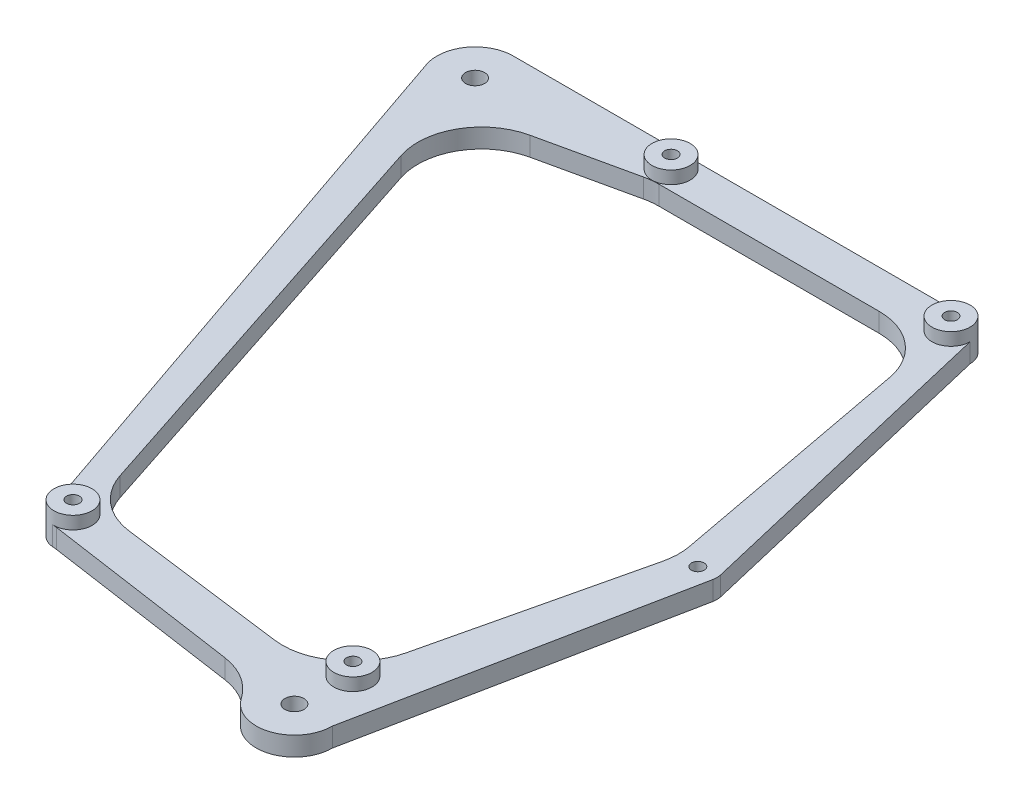
SolidWorks part; units mm, degrees
ref_plane "Front Plane" through (0, 0, 0) normal (0, 0, 1) x (1, 0, 0)
ref_plane "Top Plane" through (0, 0, 0) normal (0, 1, 0) x (1, 0, 0)
ref_plane "Right Plane" through (0, 0, 0) normal (1, 0, 0) x (0, 0, -1)
sketch "Sketch1" plane through (0, 53.5, 0) normal (0, 1, 0) x (1, 0, 0)
  circle A0 centre (-36, -88.75) radius 1.5 construction
  circle A1 centre (-36, -88.75) radius 6 construction
  circle A2 centre (35, 10.65) radius 1.5 construction
  circle A3 centre (35, 10.65) radius 6 construction
  circle A4 centre (106, -88.75) radius 1.5 construction
  circle A5 centre (106, -88.75) radius 6 construction
  circle A6 centre (-36, -88.75) radius 1.5
  circle A7 centre (-36, -88.75) radius 6
  circle A8 centre (35, 10.65) radius 1.5
  circle A9 centre (35, 10.65) radius 6
  circle A10 centre (106, -88.75) radius 1.5
  circle A11 centre (106, -88.75) radius 6
  circle A12 centre (119, -38.35) radius 1 construction
  circle A13 centre (-49, -38.35) radius 1 construction
  circle A14 centre (119, -38.35) radius 1
  circle A15 centre (-49, -38.35) radius 1
  circle A16 centre (119, -38.35) radius 3
  circle A17 centre (-49, -38.35) radius 3
  dimension "D1" = 2
  dimension "D2" = 2
extrude "AudioHolder links" add sketch "Sketch1" along normal blind 3
sketch "Limit profile" plane through (0, 53.5, 0) normal (0, -1, 0) x (1, 0, 0)
  line L4 (-47, -19.15) -> (117, -19.15)
  line L5 (117, -19.15) -> (117, 95.85)
  line L6 (117, 95.85) -> (-47, 95.85)
  line L7 (-47, 95.85) -> (-47, -19.15)
  line L8 (-47, -19.15) -> (117, -19.15)
  line L9 (117, -19.15) -> (117, 95.85)
  line L10 (117, 95.85) -> (-47, 95.85)
  line L11 (-47, 95.85) -> (-47, -19.15)
  dimension "D1" = 0
sketch "Sketch3" plane through (0, 56.5, 0) normal (0, 1, 0) x (1, 0, 0)
  line L0 (117, 19.15) -> (117, -95.85) construction
  line L1 (38.8, 17.05) -> (117, 17.05) construction
  line L2 (38.8, 17.05) -> (38.8, -83.75) construction
  line L3 (38.8, -83.75) -> (117, -83.75) construction
  line L4 (117, 17.05) -> (117, -83.75) construction
  line L5 (62.8, 13.65) -> (106.8, 13.65) construction
  line L6 (62.8, 13.65) -> (62.8, -80.35) construction
  line L7 (62.8, -80.35) -> (106.8, -80.35) construction
  line L8 (106.8, 13.65) -> (106.8, -80.35) construction
  line L10 (35, 16.65) -> (62.8, 16.65) construction
  circle A0 centre (106.8, 13.65) radius 1
  circle A1 centre (62.8, 13.65) radius 1
  circle A2 centre (62.8, -80.35) radius 1
  circle A3 centre (106.8, -80.35) radius 1
  circle A4 centre (106.8, 13.65) radius 3
  circle A5 centre (62.8, 13.65) radius 3
  circle A6 centre (62.8, -80.35) radius 3
  circle A7 centre (106.8, -80.35) radius 3
  circle A8 centre (35, 10.65) radius 6 construction
  circle A9 centre (35, 10.65) radius 6 construction
  point P4 (62.8, -33.35)
  point P9 (38.8, -33.35)
  dimension "D7" = 2
  dimension "D8" = 2
  dimension "D1" = 78.2
  dimension "D2" = 100.8
  dimension "D3" = 44
  dimension "D4" = 94
  dimension "D5" = 10.2
extrude "Modem standoffs" add sketch "Sketch3" along normal blind 2 and the other way up to surface (3 mm away) other way up to face at (106, 53.5, 94.75)
sketch "Sketch4" plane through (0, 53.5, 0) normal (0, -1, 0) x (1, 0, 0)
  line L0 (109.8, -13.65) -> (121.9197, 37.6604)
  line L1 (112, 88.75) -> (121.942, 38.9372)
  line L2 (106.8, 77.35) -> (116, 38.35)
  line L3 (116, 38.35) -> (106.8, -10.65)
  line L4 (106.8, -16.65) -> (62.8, -16.65)
  line L5 (62.8, -16.65) -> (35, -16.65)
  line L6 (100, 88.75) -> (62.8, 83.35)
  line L7 (63.1864, 77.375) -> (105.0953, 82.8186)
  line L8 (36.295, -4.7914) -> (62.8, -10.65)
  line L9 (62.8, -10.65) -> (106.8, -10.65)
  circle A0 centre (119, 38.35) radius 1 construction
  circle A1 centre (119, 38.35) radius 3 construction
  circle A2 centre (106.8, -13.65) radius 1 construction
  circle A3 centre (106.8, -13.65) radius 3 construction
  circle A4 centre (62.8, -13.65) radius 1 construction
  circle A5 centre (62.8, -13.65) radius 3 construction
  circle A6 centre (35, -10.65) radius 1.5 construction
  circle A7 centre (35, -10.65) radius 6 construction
  circle A8 centre (119, 38.35) radius 1
  arc A9 (121.9197, 37.6604) -> (121.942, 38.9372) centre (119, 38.35) ccw
  circle A10 centre (106.8, -13.65) radius 1
  arc A11 (106.8, -16.65) -> (109.8, -13.65) centre (106.8, -13.65) ccw
  circle A12 centre (62.8, -13.65) radius 1
  circle A14 centre (35, -10.65) radius 1.5
  arc A15 (36.295, -4.7914) -> (35, -16.65) centre (35, -10.65) ccw
  circle A16 centre (106, 88.75) radius 1.5 construction
  arc A17 (108.0081, 83.096) -> (105.0953, 82.8186) centre (106, 88.75) ccw construction
  circle A18 centre (106.8, 80.35) radius 3 construction
  circle A19 centre (106.8, 80.35) radius 1 construction
  circle A20 centre (62.8, 80.35) radius 1 construction
  circle A21 centre (62.8, 80.35) radius 3 construction
  circle A22 centre (106, 88.75) radius 1.5
  arc A23 (112, 88.75) -> (100, 88.75) centre (106, 88.75) ccw
  arc A24 (105.0953, 82.8186) -> (106.8, 77.35) centre (106.8, 80.35) ccw
  circle A25 centre (106.8, 80.35) radius 1
  circle A26 centre (62.8, 80.35) radius 1
  arc A27 (62.8, 83.35) -> (63.1864, 77.375) centre (62.8, 80.35) ccw
extrude "Screwhole links 1" add sketch "Sketch4" against normal up to surface (3 mm away) up to face at (105.9734, 56.5, 89.0297)
sketch "Sketch5" plane through (0, 53.5, 0) normal (0, -1, 0) x (1, 0, 0)
  line L0 (59.8063, 80.1564) -> (29.3246, -8.7032)
  line L1 (63.1864, 77.375) -> (36.295, -4.7914)
  arc A0 (62.8, 83.35) -> (63.1864, 77.375) centre (62.8, 80.35) ccw construction
  arc A1 (36.295, -4.7914) -> (35, -16.65) centre (35, -10.65) ccw construction
  arc A2 (36.295, -4.7914) -> (29.3246, -8.7032) centre (35, -10.65) ccw
  arc A3 (59.8063, 80.1564) -> (63.1864, 77.375) centre (62.8, 80.35) ccw
extrude "Screwhole links 2" add sketch "Sketch5" against normal up to surface (3 mm away) up to face at (46.8207, 56.5, -12.0048)
sketch "Sketch6" plane through (0, 53.5, 0) normal (0, -1, 0) x (1, 0, 0)
  circle A0 centre (-49, 38.35) radius 3 construction
  circle A1 centre (-36, 88.75) radius 6
  circle A2 centre (-36, 88.75) radius 6
  circle A3 centre (-49, 38.35) radius 3
  dimension "D1" = 0
extrude "Removal of unused links to layer below" cut sketch "Sketch6" against normal through all both and the other way through all
fillet "General rounding 10mm (will replace later)" radius 10 10 edges at (63.1864, 55, 77.375) (36.295, 55, -4.7914) (62.8, 55, -10.65) (106.8, 55, -10.65) (105.0953, 55, 82.8186) (106.8, 55, 77.35) (100, 55, 88.75) (62.8, 55, 83.35) (116, 55, 38.35) (59.8063, 55, 80.1564)
